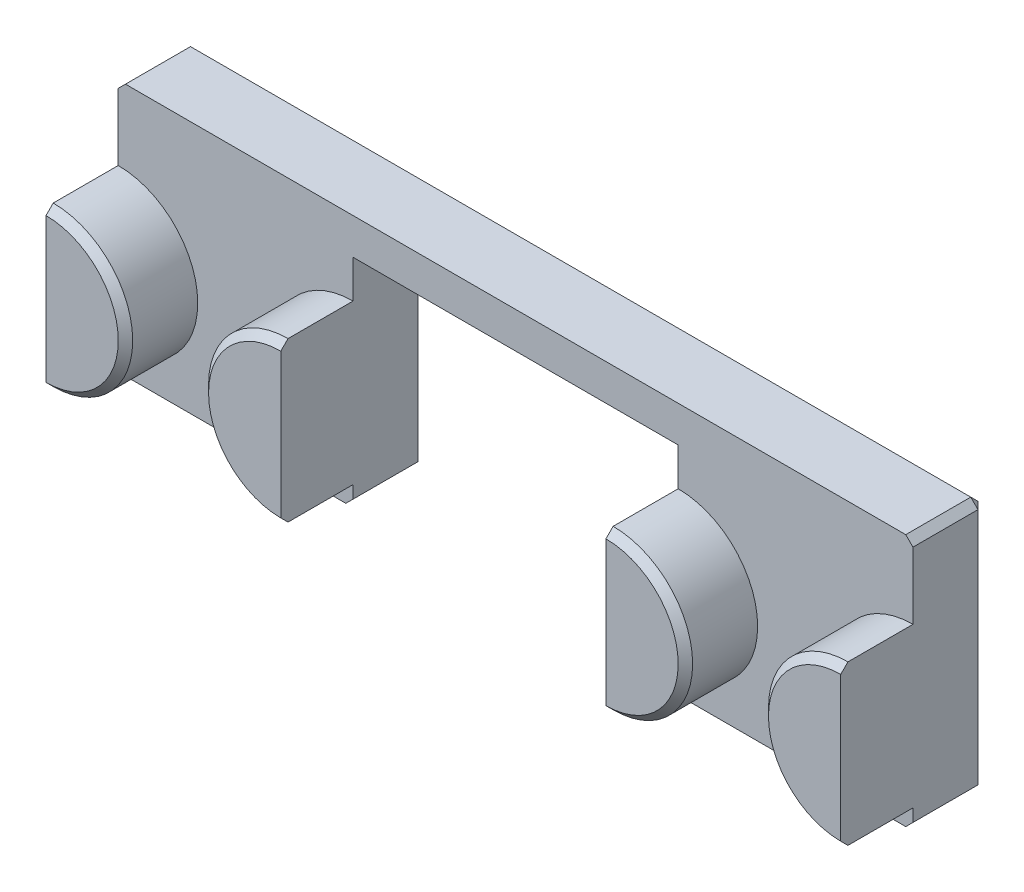
SolidWorks part; units mm, degrees
ref_plane "Front" through (0, 0, 0) normal (0, 0, 1) x (1, 0, 0)
ref_plane "Top" through (0, 0, 0) normal (0, 1, 0) x (1, 0, 0)
ref_plane "Right" through (0, 0, 0) normal (1, 0, 0) x (0, 0, -1)
sketch "Sketch1" plane through (0, 0, 0) normal (0, 0, 1) x (1, 0, 0)
  line L0 (-11, 3.5) -> (11, 3.5)
  line L5 (11, 3.5) -> (11, -3.5)
  line L6 (11, -3.5) -> (4.5, -3.5)
  line L7 (4.5, -3.5) -> (4.5, 2.5)
  line L8 (4.5, 2.5) -> (-4.5, 2.5)
  line L9 (-4.5, 2.5) -> (-4.5, -3.5)
  line L10 (-4.5, -3.5) -> (-11, -3.5)
  line L11 (-11, -3.5) -> (-11, 3.5)
  line L12 (4.5, -3.5) -> (11, -3.5) construction
  line L13 (10.8, 3.5) -> (-10.8, 3.5) construction
  point P5 (0, 0)
  point P15 (-10, -3.5)
  point P17 (0, 0)
  point P18 (10, -3.5)
extrude "Boss-Extrude1" add sketch "Sketch1" against normal blind 2
sketch "Sketch2" plane through (0, 0, 0) normal (0, 0, 1) x (1, 0, 0)
  line L0 (11, 3.5) -> (11, -3.5) construction
  line L1 (11, 3.5) -> (11, -3.5)
  line L2 (11, -3.5) -> (4.5, -3.5) construction
  line L3 (11, -3.5) -> (4.5, -3.5)
  circle A1 centre (11, -0.75) radius 2.3
  circle A2 centre (11, -0.75) radius 2.3
  circle A4 centre (11, -0.75) radius 2.2
  circle A5 centre (11, -0.75) radius 2.2
  dimension "D1" = 0
  dimension "D2" = 0.1
extrude "Boss-Extrude2" add sketch "Sketch2" along normal blind 2 contours A5 region at (10.0663, -0.75, 0)
ref_plane "Plane1" through (7.75, 0, 0) normal (1, 0, 0) x (0, 0, -1)
mirror "Mirror1" about plane through (7.75, 0, 0) normal (1, 0, 0) of "Boss-Extrude2"
mirror "Mirror2" about plane through (0, 0, 0) normal (1, 0, 0) of "Mirror1"
chamfer "Deburs" distance 0.2 angle 45 18 edges at (0, 3.5, -2) (11, 3.5, -1) (11, 0, -2) (11, -3.5, -1) (7.75, -3.5, -2) (4.5, -3.5, -1) (4.5, -0.5, -2) (0, 2.5, -2) (-4.5, -0.5, -2) (-4.5, -3.5, -1) (-7.75, -3.5, -2) (-11, 3.5, -1) (-11, 0, -2) (-11, -3.5, -1) (8.8, -0.75, 2) (6.7, -0.75, 2) (-6.7, -0.75, 2) (-8.8, -0.75, 2)
